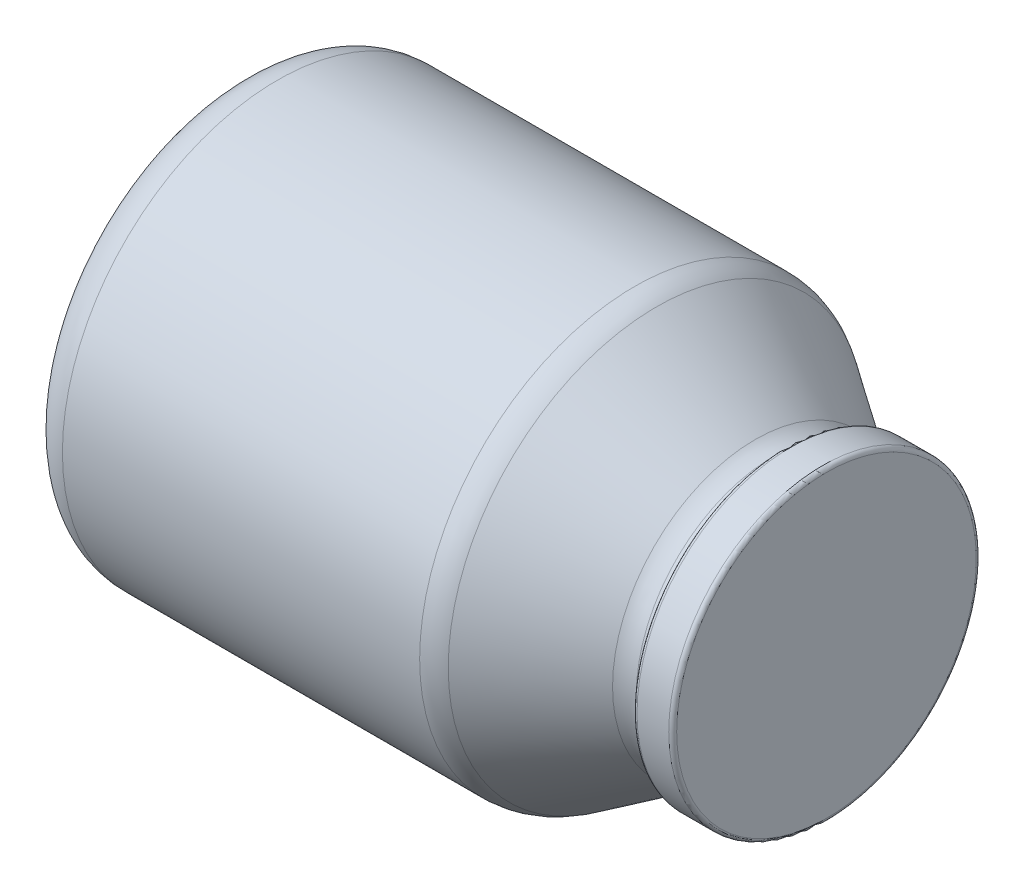
SolidWorks part; units mm, degrees
ref_plane "Front Plane" through (0, 0, 0) normal (0, 0, 1) x (1, 0, 0)
ref_plane "Top Plane" through (0, 0, 0) normal (0, 1, 0) x (1, 0, 0)
ref_plane "Right Plane" through (0, 0, 0) normal (1, 0, 0) x (0, 0, -1)
sketch "Sketch1" plane through (0, 0, 0) normal (0, 0, 1) x (1, 0, 0)
  line L0 (0, 0) -> (288.4894, 0) construction
  line L1 (0, 0) -> (0, 53)
  line L2 (12, 65) -> (120, 65)
  line L3 (126.6398, 62.9957) -> (156.4855, 43.1703)
  line L4 (162.0187, 41.5) -> (166, 41.5)
  line L5 (166, 41.5) -> (166, 46.5)
  line L6 (166, 46.5) -> (178, 46.5)
  line L7 (178, 46.5) -> (178, 0)
  line L8 (178, 0) -> (0, 0)
  arc A0 (0, 53) -> (12, 65) centre (12, 53) cw
  arc A1 (120, 65) -> (126.6398, 62.9957) centre (120, 53) cw
  arc A2 (156.4855, 43.1703) -> (162.0187, 41.5) centre (162.0187, 51.5) ccw
  point P22 (159, 41.5)
  dimension "D7" = 12
  dimension "D9" = 10
  dimension "D10" = 12
  dimension "D1" = 178
  dimension "D2" = 93
  dimension "D3" = 12
  dimension "D4" = 130
  dimension "D5" = 5
  dimension "D6" = 7
  dimension "D8" = 120
revolve "Revolve1" add sketch "Sketch1" angle 360 about L0
fillet "Fillet1" radius 1.2 2 edges at (178, 0, 46.5) (166, 0, 46.5)
ref_axis "Axis1" through (120, 0, 0) along (-1, 0, 0)
